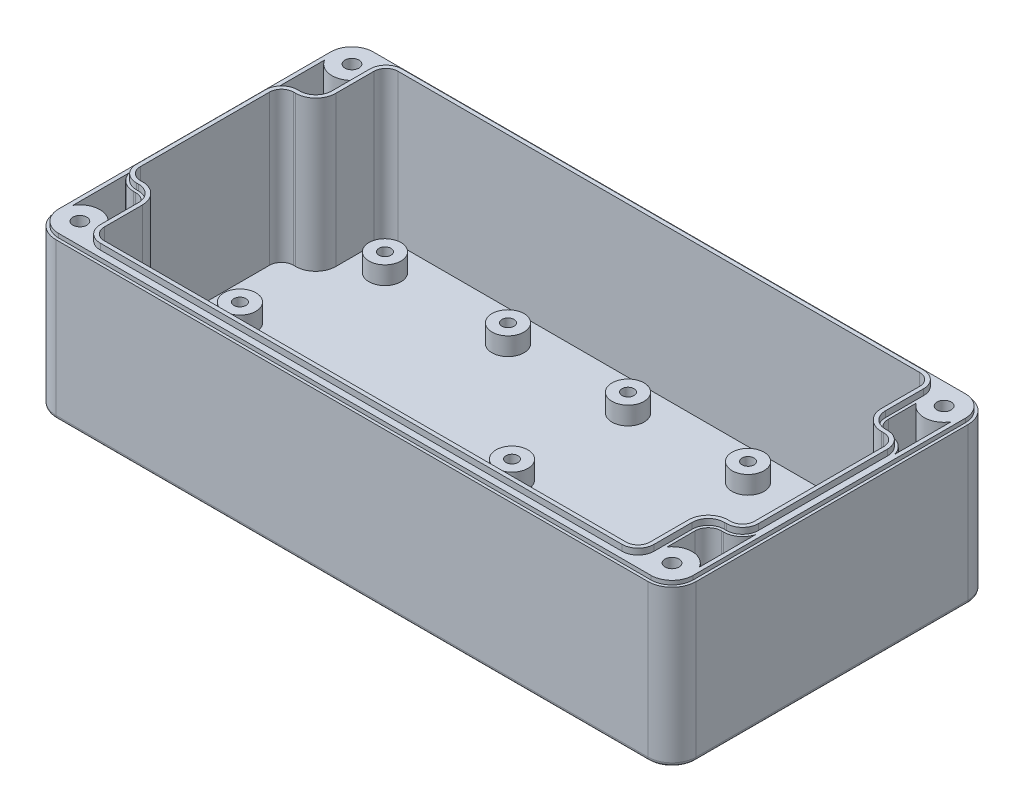
SolidWorks part; units mm, degrees
ref_plane "Спереди" through (0, 0, 0) normal (0, 0, 1) x (1, 0, 0)
ref_plane "Сверху" through (0, 0, 0) normal (0, 1, 0) x (1, 0, 0)
ref_plane "Справа" through (0, 0, 0) normal (1, 0, 0) x (0, 0, -1)
sketch "Эскиз1" plane through (0, 0, 0) normal (0, 1, 0) x (1, 0, 0)
  line L1 (-74, 40) -> (74, 40)
  line L2 (-80, 34) -> (-80, -34)
  line L3 (-74, -40) -> (74, -40)
  line L4 (80, 34) -> (80, -34)
  line L5 (-80, 40) -> (80, -40) construction
  line L6 (-80, -40) -> (80, 40) construction
  arc A0 (74, 40) -> (80, 34) centre (74, 34) cw
  arc A1 (80, -34) -> (74, -40) centre (74, -34) cw
  arc A2 (-74, -40) -> (-80, -34) centre (-74, -34) cw
  arc A3 (-80, 34) -> (-74, 40) centre (-74, 34) cw
  point P0 (0, 0)
  dimension "D3" = 6
  dimension "D1" = 160
  dimension "D2" = 80
extrude "Бобышка-Вытянуть1" add sketch "Эскиз1" along normal blind 40
sketch "Эскиз2" plane through (0, 0, 0) normal (0, 1, 0) x (1, 0, 0)
  line L0 (-68.2, 33.7) -> (-68.2, 24.15)
  line L1 (-73.2, 19.15) -> (-73.75, 19.15)
  line L2 (-76.75, 16.15) -> (-76.75, -16.15)
  line L3 (-73.75, -19.15) -> (-73.2, -19.15)
  line L4 (-68.2, -24.15) -> (-68.2, -33.7)
  line L5 (-65.2, -36.7) -> (65.2, -36.7)
  line L6 (68.2, -33.7) -> (68.2, -24.15)
  line L7 (73.2, -19.15) -> (73.75, -19.15)
  line L8 (76.75, -16.15) -> (76.75, 16.15)
  line L9 (73.75, 19.15) -> (73.2, 19.15)
  line L10 (68.2, 24.15) -> (68.2, 33.7)
  line L11 (65.2, 36.7) -> (-65.2, 36.7)
  line L12 (-76.75, 0) -> (76.75, 0) construction
  line L13 (0, 36.7) -> (0, -36.7) construction
  arc A0 (68.2, 24.15) -> (73.2, 19.15) centre (73.2, 24.15) ccw
  arc A1 (73.2, -19.15) -> (68.2, -24.15) centre (73.2, -24.15) ccw
  arc A2 (-68.2, -24.15) -> (-73.2, -19.15) centre (-73.2, -24.15) ccw
  arc A3 (-73.2, 19.15) -> (-68.2, 24.15) centre (-73.2, 24.15) ccw
  arc A4 (65.2, 36.7) -> (68.2, 33.7) centre (65.2, 33.7) cw
  arc A5 (73.75, 19.15) -> (76.75, 16.15) centre (73.75, 16.15) cw
  arc A6 (76.75, -16.15) -> (73.75, -19.15) centre (73.75, -16.15) cw
  arc A7 (68.2, -33.7) -> (65.2, -36.7) centre (65.2, -33.7) cw
  arc A8 (-65.2, -36.7) -> (-68.2, -33.7) centre (-65.2, -33.7) cw
  arc A9 (-73.75, -19.15) -> (-76.75, -16.15) centre (-73.75, -16.15) cw
  arc A10 (-76.75, 16.15) -> (-73.75, 19.15) centre (-73.75, 16.15) cw
  arc A11 (-68.2, 33.7) -> (-65.2, 36.7) centre (-65.2, 33.7) cw
  dimension "D4" = 153.5
  dimension "D1" = 5
  dimension "D2" = 3
  dimension "D3" = 73.4
  dimension "D5" = 38.3
  dimension "D6" = 136.4
extrude "Вырез-Вытянуть1" cut sketch "Эскиз2" along normal up to surface (40 mm away) from offset 4 up to face at (0, 40, 0)
sketch "Эскиз3" plane through (0, 0, 0) normal (0, 1, 0) x (1, 0, 0)
  line L8 (-78.3, 34) -> (-78.3, -34)
  line L9 (-74, -38.3) -> (74, -38.3)
  line L10 (78.3, -34) -> (78.3, 34)
  line L11 (74, 38.3) -> (-74, 38.3)
  line L12 (-78.3, 34) -> (-78.3, -34)
  line L13 (-74, -38.3) -> (74, -38.3)
  line L14 (78.3, -34) -> (78.3, 34)
  line L15 (74, 38.3) -> (-74, 38.3)
  line L36 (69.9, 24.15) -> (69.9, 33.7)
  line L37 (73.75, 20.85) -> (73.2, 20.85)
  line L38 (78.45, -16.15) -> (78.45, 16.15)
  line L39 (73.2, -20.85) -> (73.75, -20.85)
  line L40 (69.9, -33.7) -> (69.9, -24.15)
  line L41 (-65.2, -38.4) -> (65.2, -38.4)
  line L42 (-69.9, -24.15) -> (-69.9, -33.7)
  line L43 (-73.75, -20.85) -> (-73.2, -20.85)
  line L44 (-78.45, 16.15) -> (-78.45, -16.15)
  line L45 (-73.2, 20.85) -> (-73.75, 20.85)
  line L46 (-69.9, 33.7) -> (-69.9, 24.15)
  line L47 (65.2, 38.4) -> (-65.2, 38.4)
  line L48 (69.9, 24.15) -> (69.9, 33.7)
  line L49 (73.75, 20.85) -> (73.2, 20.85)
  line L50 (78.45, -16.15) -> (78.45, 16.15)
  line L51 (73.2, -20.85) -> (73.75, -20.85)
  line L52 (69.9, -33.7) -> (69.9, -24.15)
  line L53 (-65.2, -38.4) -> (65.2, -38.4)
  line L54 (-69.9, -24.15) -> (-69.9, -33.7)
  line L55 (-73.75, -20.85) -> (-73.2, -20.85)
  line L56 (-78.45, 16.15) -> (-78.45, -16.15)
  line L57 (-73.2, 20.85) -> (-73.75, 20.85)
  line L58 (-69.9, 33.7) -> (-69.9, 24.15)
  line L59 (65.2, 38.4) -> (-65.2, 38.4)
  circle A0 centre (-74, 34) radius 5
  arc A8 (-74, 38.3) -> (-78.3, 34) centre (-74, 34) ccw
  arc A9 (-78.3, -34) -> (-74, -38.3) centre (-74, -34) ccw
  arc A10 (74, -38.3) -> (78.3, -34) centre (74, -34) ccw
  arc A11 (78.3, 34) -> (74, 38.3) centre (74, 34) ccw
  arc A12 (-74, 38.3) -> (-78.3, 34) centre (-74, 34) ccw
  arc A13 (-78.3, -34) -> (-74, -38.3) centre (-74, -34) ccw
  arc A14 (74, -38.3) -> (78.3, -34) centre (74, -34) ccw
  arc A15 (78.3, 34) -> (74, 38.3) centre (74, 34) ccw
  arc A36 (69.9, 33.7) -> (65.2, 38.4) centre (65.2, 33.7) ccw
  arc A37 (69.9, 24.15) -> (73.2, 20.85) centre (73.2, 24.15) ccw
  arc A38 (78.45, 16.15) -> (73.75, 20.85) centre (73.75, 16.15) ccw
  arc A39 (73.75, -20.85) -> (78.45, -16.15) centre (73.75, -16.15) ccw
  arc A40 (73.2, -20.85) -> (69.9, -24.15) centre (73.2, -24.15) ccw
  arc A41 (65.2, -38.4) -> (69.9, -33.7) centre (65.2, -33.7) ccw
  arc A42 (-69.9, -33.7) -> (-65.2, -38.4) centre (-65.2, -33.7) ccw
  arc A43 (-69.9, -24.15) -> (-73.2, -20.85) centre (-73.2, -24.15) ccw
  arc A44 (-78.45, -16.15) -> (-73.75, -20.85) centre (-73.75, -16.15) ccw
  arc A45 (-73.75, 20.85) -> (-78.45, 16.15) centre (-73.75, 16.15) ccw
  arc A46 (-73.2, 20.85) -> (-69.9, 24.15) centre (-73.2, 24.15) ccw
  arc A47 (-65.2, 38.4) -> (-69.9, 33.7) centre (-65.2, 33.7) ccw
  arc A48 (69.9, 33.7) -> (65.2, 38.4) centre (65.2, 33.7) ccw
  arc A49 (69.9, 24.15) -> (73.2, 20.85) centre (73.2, 24.15) ccw
  arc A50 (78.45, 16.15) -> (73.75, 20.85) centre (73.75, 16.15) ccw
  arc A51 (73.75, -20.85) -> (78.45, -16.15) centre (73.75, -16.15) ccw
  arc A52 (73.2, -20.85) -> (69.9, -24.15) centre (73.2, -24.15) ccw
  arc A53 (65.2, -38.4) -> (69.9, -33.7) centre (65.2, -33.7) ccw
  arc A54 (-69.9, -33.7) -> (-65.2, -38.4) centre (-65.2, -33.7) ccw
  arc A55 (-69.9, -24.15) -> (-73.2, -20.85) centre (-73.2, -24.15) ccw
  arc A56 (-78.45, -16.15) -> (-73.75, -20.85) centre (-73.75, -16.15) ccw
  arc A57 (-73.75, 20.85) -> (-78.45, 16.15) centre (-73.75, 16.15) ccw
  arc A58 (-73.2, 20.85) -> (-69.9, 24.15) centre (-73.2, 24.15) ccw
  arc A59 (-65.2, 38.4) -> (-69.9, 33.7) centre (-65.2, 33.7) ccw
  dimension "D3" = 10
  dimension "D1" = 1.7
  dimension "D2" = 1.7
extrude "Вырез-Вытянуть2" cut sketch "Эскиз3" along normal up to surface (40 mm away) from offset 2.5 contours L57 A58 L58 A0 L12 A57 region at (-74.3973, 0, -25.1085) up to face at (0, 40, 0)
mirror "Зеркальное отражение1" about plane through (0, 0, 0) normal (0, 0, 1) of "Вырез-Вытянуть2"
mirror "Зеркальное отражение2" about plane through (0, 0, 0) normal (1, 0, 0) of "Зеркальное отражение1"
extrude "Вытянуть-Тонкостенный1" add sketch "Эскиз2<2>" along normal blind 1.5 from surface thin contours L11 A11 L0 A3 L1 A10 L2 A9 L3 A2 L4 A8 L5 A7 L6 A1 L7 A6 L8 A5 L9 A0 L10 A4 starting at face at (-73.8922, 40, 23.9281) thin type one direction wall 1
sketch "Эскиз2<2>" plane through (0, 0, 0) normal (0, 1, 0) x (1, 0, 0) same geometry as "Эскиз2"
sketch "Эскиз6" plane through (0, 0, 0) normal (0, 1, 0) x (1, 0, 0)
  circle A0 centre (-74, 34) radius 3.75
  circle A1 centre (-74, -34) radius 3.75
  circle A2 centre (74, -34) radius 3.75
  circle A3 centre (74, 34) radius 3.75
  dimension "D1" = 7.5
extrude "Вырез-Вытянуть3" cut sketch "Эскиз6" along normal blind 32
sketch "Эскиз7" plane through (0, 0, 0) normal (0, 1, 0) x (1, 0, 0)
  circle A0 centre (-74, 34) radius 1.75
  circle A1 centre (-74, -34) radius 1.75
  circle A2 centre (74, -34) radius 1.75
  circle A3 centre (74, 34) radius 1.75
  dimension "D1" = 3.5
extrude "Вырез-Вытянуть4" cut sketch "Эскиз7" along normal up to surface (40 mm away) up to face at (0, 40, 0)
fillet "Скругление1" radius 1 8 edges at (78.2426, 0, -38.2426) (80, 0, 0) (78.2426, 0, 38.2426) (0, 0, 40) (-78.2426, 0, 38.2426) (-80, 0, 0) (-78.2426, 0, -38.2426) (0, 0, -40)
sketch "Эскиз8" plane through (0, 0, 0) normal (0, 1, 0) x (1, 0, 0)
  line L1 (-74.15, 25.1) -> (74.15, 25.1) construction
  line L2 (-74.15, 25.1) -> (-74.15, -25.1) construction
  line L3 (-74.15, -25.1) -> (74.15, -25.1) construction
  line L4 (74.15, 25.1) -> (74.15, -25.1) construction
  line L5 (-74.15, 25.1) -> (74.15, -25.1) construction
  line L6 (-74.15, -25.1) -> (74.15, 25.1) construction
  circle A0 centre (-74.15, 25.1) radius 2.1
  circle A1 centre (-74.15, -25.1) radius 2.1
  circle A2 centre (74.15, -25.1) radius 2.1
  circle A3 centre (74.15, 25.1) radius 2.1
  point P0 (0, 0)
  dimension "D3" = 4.2
  dimension "D1" = 50.2
  dimension "D2" = 148.3
extrude "Вырез-Вытянуть5" cut sketch "Эскиз8" along normal up to surface (2.5 mm away) up to face at (-73.8922, 2.5, -23.9281)
extrude "Вырез-Вытянуть-Тонкостенный1" cut sketch "Эскиз1<2>" against normal blind 1 from surface thin starting at face at (74, 40, 32.25) thin type one direction reverse wall 0.7
sketch "Эскиз1<2>" plane through (0, 0, 0) normal (0, 1, 0) x (1, 0, 0) same geometry as "Эскиз1"
sketch "Эскиз9" plane through (0, 0, 0) normal (0, 1, 0) x (1, 0, 0)
  line L0 (0, 0) -> (0, 10.7849) construction
  line L1 (0, 0) -> (-13.1073, 0) construction
  point P0 (-60.75, 29)
  point P1 (0, 29)
  point P3 (-30, 29)
  point P4 (0, 0)
  point P7 (-68, 0)
  point P9 (68, 0)
  point P10 (30, 29)
  point P11 (60.75, 29)
  point P12 (60.75, -29)
  point P13 (30, -29)
  point P14 (-30, -29)
  point P16 (0, -29)
  point P17 (-60.75, -29)
  dimension "D1" = 29
  dimension "D2" = 30
  dimension "D3" = 60.75
  dimension "D4" = 68
sketch "Эскиз10" plane through (0, 0, 0) normal (0, 1, 0) x (1, 0, 0)
  circle A0 centre (-60.75, 29) radius 4
  circle A1 centre (-60.75, 29) radius 1.5
  dimension "D1" = 8
  dimension "D2" = 3
extrude "Бобышка-Вытянуть2" add sketch "Эскиз10" along normal blind 8.5
pattern_sketch "Эскиз-Массив1" of "Бобышка-Вытянуть2" driven by "Эскиз9"
